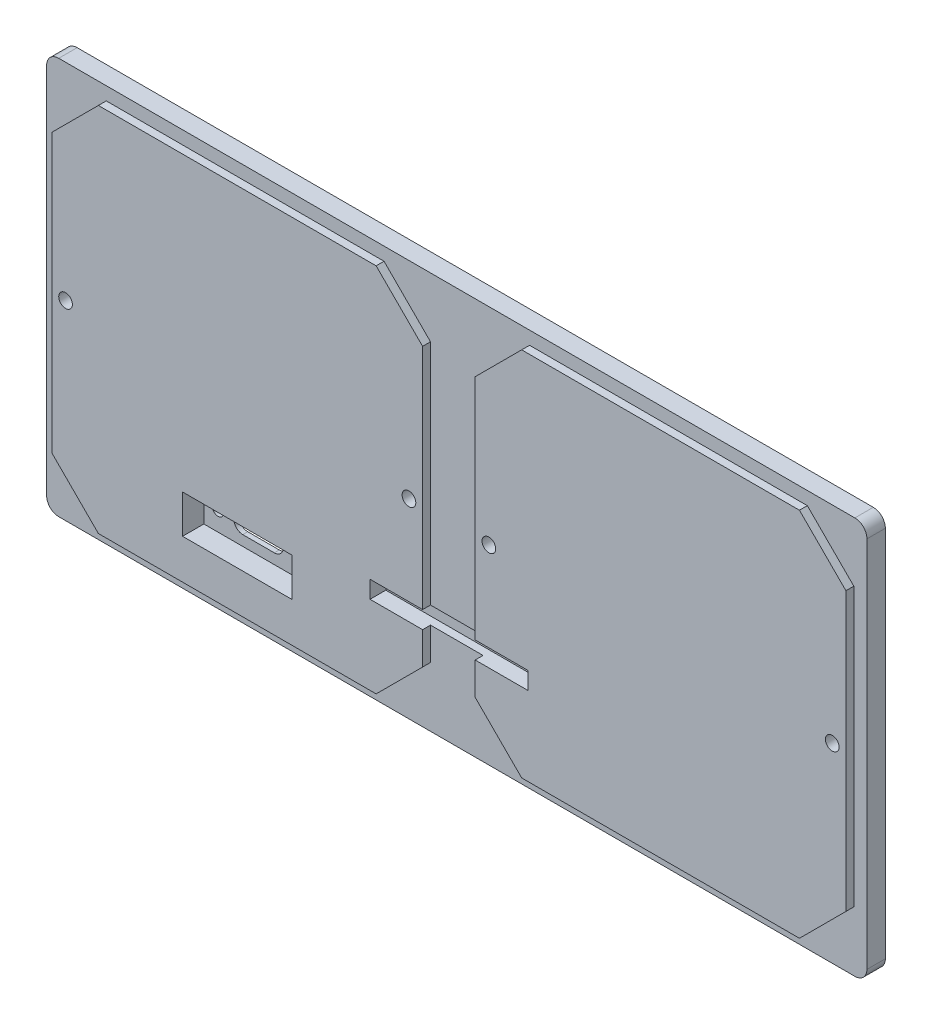
SolidWorks part; units mm, degrees
ref_plane "前视基准面" through (0, 0, 0) normal (0, 0, 1) x (1, 0, 0)
ref_plane "上视基准面" through (0, 0, 0) normal (0, 1, 0) x (1, 0, 0)
ref_plane "右视基准面" through (0, 0, 0) normal (1, 0, 0) x (0, 0, -1)
sketch "草图1" plane through (0, 0, 0) normal (0, 0, 1) x (1, 0, 0)
  line L0 (-72.9, 0) -> (-7.6, 0) construction
  line L1 (-78, -37.75) -> (78, -37.75)
  line L2 (-78, -37.75) -> (-78, 37.75)
  line L3 (-78, 37.75) -> (78, 37.75)
  line L4 (78, -37.75) -> (78, 37.75)
  line L5 (-78, -37.75) -> (78, 37.75) construction
  line L6 (-78, 37.75) -> (78, -37.75) construction
  line L7 (-78, 42.7368) -> (-2.5, 42.7368) construction
  line L8 (78, 42.6441) -> (2.5, 42.6441) construction
  line L9 (0, 0) -> (0, -21.796) construction
  circle A0 centre (-72.9, 0) radius 1.3
  circle A1 centre (-7.6, 0) radius 1.3
  circle A2 centre (7.6, 0) radius 1.3
  circle A3 centre (72.9, 0) radius 1.3
  point P0 (0, 0)
  point P11 (-78, 0)
  point P15 (-40.25, 0)
  point P16 (-40.25, 42.7368)
  dimension "D1" = 2.6
  dimension "D2" = 75.5
  dimension "D3" = 5
  dimension "D4" = 65.3
  dimension "D5" = 75.5
extrude "凸台-拉伸1" add sketch "草图1" along normal blind 5
fillet "圆角1" radius 2.3 4 edges at (78, -37.75, 2.5) (-78, -37.75, 2.5) (78, 37.75, 2.5) (-78, 37.75, 2.5)
sketch "草图2" plane through (0, 0, 5) normal (0, 0, 1) x (1, 0, 0)
  line L1 (-75.5, 26.4112) -> (-75.5, -26.4112)
  line L2 (-78, 42.7368) -> (-2.5, 42.7368) construction
  line L3 (-66.6612, 35.25) -> (-75.5, 26.4112)
  line L5 (0, 0) -> (0, 25.0604) construction
  line L6 (66.6612, 35.25) -> (75.5, 26.4112)
  line L12 (-66.6612, 35.25) -> (-13.8388, 35.25)
  line L13 (66.6612, 35.25) -> (13.8388, 35.25)
  line L14 (-13.8388, 35.25) -> (-5, 26.4112)
  line L15 (-5, 26.4112) -> (-5, -26.4112)
  line L16 (-75.7, -37.75) -> (75.7, -37.75)
  line L17 (78, -35.45) -> (78, 35.45)
  line L18 (75.7, 37.75) -> (-75.7, 37.75)
  line L19 (-78, 35.45) -> (-78, -35.45)
  line L20 (-75.7, -37.75) -> (75.7, -37.75)
  line L21 (78, -35.45) -> (78, 35.45)
  line L22 (75.7, 37.75) -> (-75.7, 37.75)
  line L23 (-78, 35.45) -> (-78, -35.45)
  line L24 (-5, -26.4112) -> (-13.8388, -35.25)
  line L25 (-13.8388, -35.25) -> (-66.6612, -35.25)
  line L26 (-66.6612, -35.25) -> (-75.5, -26.4112)
  line L27 (13.8388, 35.25) -> (5, 26.4112)
  line L28 (5, 26.4112) -> (5, -26.4112)
  line L29 (5, -26.4112) -> (13.8388, -35.25)
  line L30 (13.8388, -35.25) -> (66.6612, -35.25)
  line L31 (66.6612, -35.25) -> (75.5, -26.4112)
  line L32 (75.5, 26.4112) -> (75.5, -26.4112)
  arc A4 (75.7, -37.75) -> (78, -35.45) centre (75.7, -35.45) ccw
  arc A5 (78, 35.45) -> (75.7, 37.75) centre (75.7, 35.45) ccw
  arc A6 (-75.7, 37.75) -> (-78, 35.45) centre (-75.7, 35.45) ccw
  arc A7 (-78, -35.45) -> (-75.7, -37.75) centre (-75.7, -35.45) ccw
  arc A8 (75.7, -37.75) -> (78, -35.45) centre (75.7, -35.45) ccw
  arc A9 (78, 35.45) -> (75.7, 37.75) centre (75.7, 35.45) ccw
  arc A10 (-75.7, 37.75) -> (-78, 35.45) centre (-75.7, 35.45) ccw
  arc A11 (-78, -35.45) -> (-75.7, -37.75) centre (-75.7, -35.45) ccw
  point P13 (-40.25, 42.7368)
  point P16 (-40.25, 35.25)
  dimension "D1" = 135
  dimension "D2" = 12.5
  dimension "D3" = 2.5
  dimension "D4" = 2.5
  dimension "D6" = 2.5
  dimension "D5" = 0
extrude "切除-拉伸1" cut sketch "草图2" against normal blind 1.5
sketch "草图5" plane through (0, 0, 0) normal (0, 0, -1) x (-1, 0, 0)
  circle A0 centre (72.9, 0) radius 1.3 construction
  circle A1 centre (7.6, 0) radius 1.3 construction
  circle A2 centre (-7.6, 0) radius 1.3 construction
  circle A3 centre (-72.9, 0) radius 1.3 construction
  circle A4 centre (72.9, 0) radius 1.3
  circle A5 centre (7.6, 0) radius 1.3
  circle A6 centre (-7.6, 0) radius 1.3
  circle A7 centre (-72.9, 0) radius 1.3
  circle A8 centre (72.9, 0) radius 2.55
  circle A9 centre (7.6, 0) radius 2.55
  circle A10 centre (-7.6, 0) radius 2.55
  circle A11 centre (-72.9, 0) radius 2.55
  dimension "D1" = 1.25
extrude "切除-拉伸4" cut sketch "草图5" against normal offset from surface (2.8 mm away) 2.2 up to face at (71.6, 0, 5)
sketch "草图3" plane through (0, 0, 0) normal (0, 0, -1) x (-1, 0, 0)
  line L0 (37.25, -24.05) -> (43.25, -24.05) construction
  line L1 (37.25, -22.35) -> (43.25, -22.35)
  line L2 (37.25, -25.75) -> (43.25, -25.75)
  line L3 (75.7, -37.75) -> (-75.7, -37.75) construction
  line L4 (78, 42.7368) -> (2.5, 42.7368) construction
  line L5 (40.25, -24.05) -> (40.25, -16.0574) construction
  arc A0 (37.25, -22.35) -> (37.25, -25.75) centre (37.25, -24.05) ccw
  arc A1 (43.25, -25.75) -> (43.25, -22.35) centre (43.25, -24.05) ccw
  circle A2 centre (47.95, -24.05) radius 1.05
  circle A3 centre (32.55, -24.05) radius 1.05
  point P2 (40.25, -24.05)
  point P11 (40.25, 42.7368)
  dimension "D2" = 9.4
  dimension "D4" = 2.1
  dimension "D1" = 3.4
  dimension "D3" = 12
  dimension "D5" = 3
extrude "切除-拉伸2" cut sketch "草图3" against normal through all
sketch "草图4" plane through (0, 0, 5) normal (0, 0, 1) x (1, 0, 0)
  line L1 (-50.65, -27.7) -> (-29.85, -27.7)
  line L2 (-50.65, -27.7) -> (-50.65, -20.4)
  line L3 (-50.65, -20.4) -> (-29.85, -20.4)
  line L4 (-29.85, -27.7) -> (-29.85, -20.4)
  line L5 (-50.65, -27.7) -> (-29.85, -20.4) construction
  line L6 (-50.65, -20.4) -> (-29.85, -27.7) construction
  point P0 (-40.25, -24.05)
  dimension "D1" = 7.3
  dimension "D2" = 20.8
extrude "切除-拉伸3" cut sketch "草图4" against normal offset from surface (4.05 mm away) 0.95 up to face at (-31.5, -24.05, 0)
sketch "草图6" plane through (0, 0, 5) normal (0, 0, 1) x (1, 0, 0)
  line L0 (-66.6612, -35.25) -> (-13.8388, -35.25) construction
  line L1 (-15, -16.95) -> (15, -16.95)
  line L2 (-15, -16.95) -> (-15, -20.25)
  line L3 (-15, -20.25) -> (15, -20.25)
  line L4 (15, -16.95) -> (15, -20.25)
  point P4 (0, -16.95)
  dimension "D1" = 3.3
  dimension "D2" = 30
  dimension "D3" = 15
extrude "切除-拉伸5" cut sketch "草图6" against normal offset from surface (3 mm away) 1.5 up to face at (40.25, 0, 3.5) offset beyond the face yes
